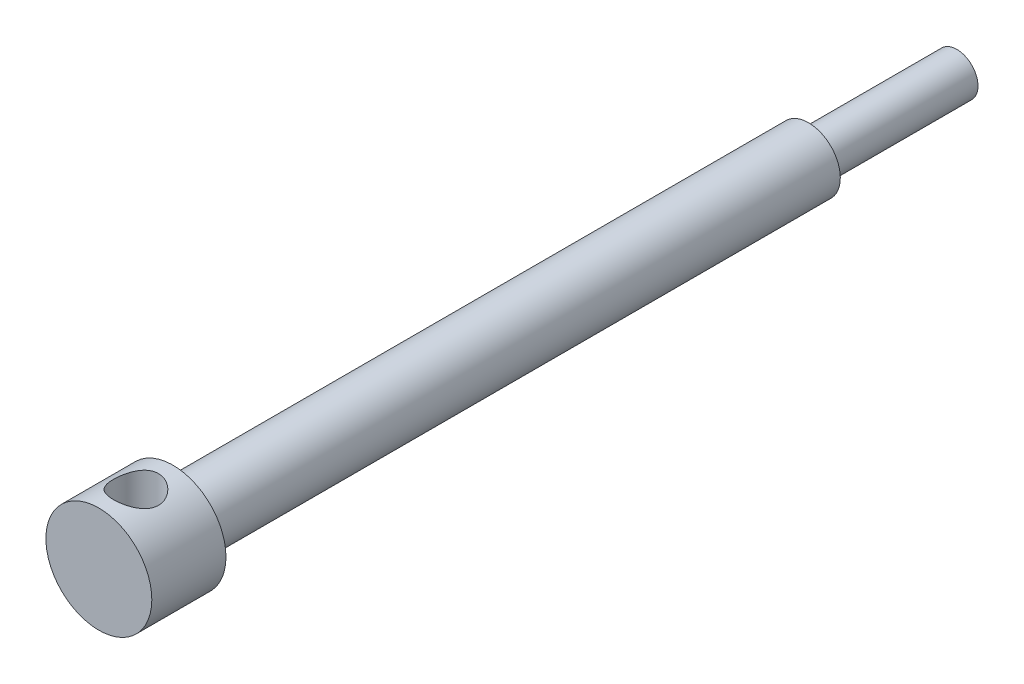
SolidWorks part; units mm, degrees
material "Alloy Steel"
ref_plane "Front Plane" through (0, 0, 0) normal (0, 0, 1) x (1, 0, 0)
ref_plane "Top Plane" through (0, 0, 0) normal (0, 1, 0) x (1, 0, 0)
ref_plane "Right Plane" through (0, 0, 0) normal (1, 0, 0) x (0, 0, -1)
sketch "Sketch1" plane through (0, 0, 0) normal (1, 0, 0) x (0, 0, -1)
  line L0 (-83.2643, 0) -> (88.7628, 0) construction
  line L1 (-5.5562, 0) -> (-5.5562, 7.9375)
  line L2 (-5.5562, 7.9375) -> (5.5562, 7.9375)
  line L3 (5.5562, 7.9375) -> (5.5563, 4.7625)
  line L4 (5.5563, 4.7625) -> (100.8063, 4.7625)
  line L5 (100.8063, 4.7625) -> (100.8063, 3.175)
  line L6 (100.8063, 3.175) -> (123.0312, 3.175)
  line L7 (123.0312, 3.175) -> (123.0312, 0)
  line L8 (123.0312, 0) -> (-5.5562, 0)
  line L9 (0, 7.9375) -> (0, -7.9375) construction
  dimension "D1" = 11.1125
  dimension "D2" = 106.3625
  dimension "D3" = 128.5875
  dimension "D4" = 15.875
  dimension "D5" = 9.525
  dimension "D6" = 6.35
revolve "Revolve1" add sketch "Sketch1" angle 360 about L0
cosmetic thread "Cosmetic Thread2" parameters "D2"=8.2652
cosmetic thread "Cosmetic Thread3" parameters "D2"=8.2652
hole_wizard "#97 (0.0059) Diameter Hole1" positions "3DSketch1" profile "Sketch2" hole size "#97" standard "Ansi Inch" end condition through all
sketch3d "3DSketch1"
  point P0 (0, 0, 0)
  point P4 (0, -7.9375, 0)
sketch "Sketch2" plane through (0, -7.9375, 0) normal (1, 0, 0) x (0, 0, -1)
  line L0 (0, 0) -> (0, 15.875)
  line L1 (0, 15.875) -> (3.3782, 15.875)
  line L2 (3.3782, 15.875) -> (3.3782, 0)
  line L5 (3.3782, 0) -> (0, 0)
  line L11 (0, -6.35) -> (0, 107.95) construction
  dimension "Thru Hole Dia." = 6.7564
  dimension "Thru Hole Depth" = 15.875
